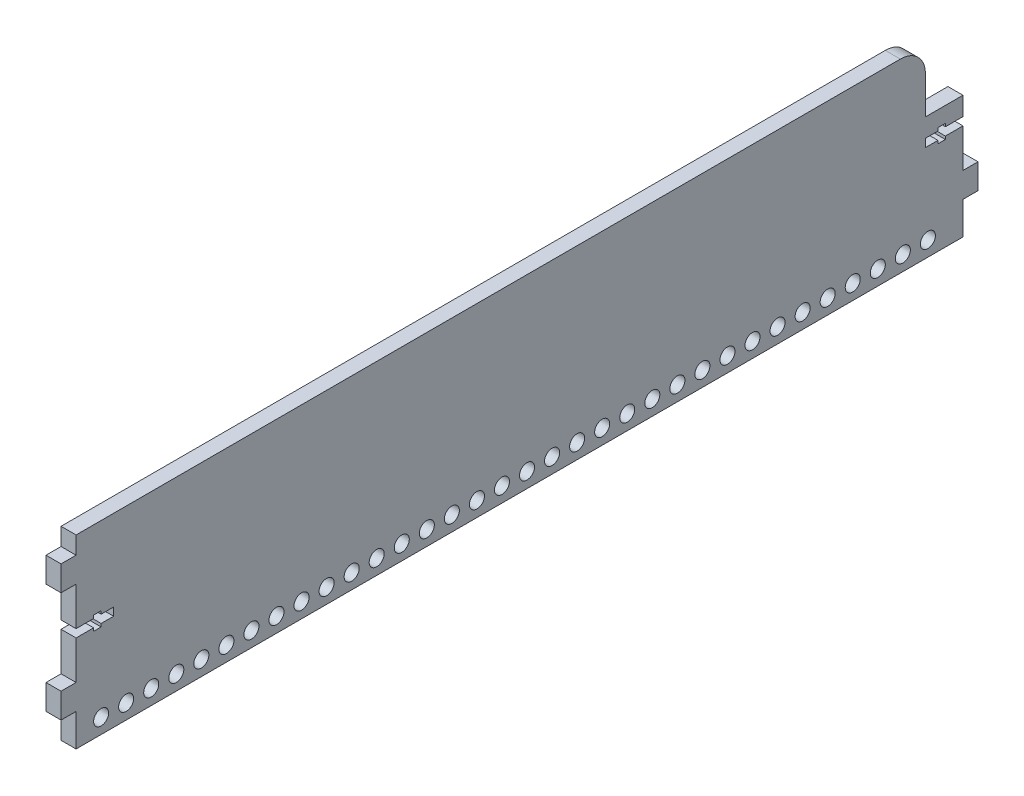
SolidWorks part; units mm, degrees
ref_plane "Front Plane" through (0, 0, 0) normal (0, 0, 1) x (1, 0, 0)
ref_plane "Top Plane" through (0, 0, 0) normal (0, 1, 0) x (1, 0, 0)
ref_plane "Right Plane" through (0, 0, 0) normal (1, 0, 0) x (0, 0, -1)
sketch "Sketch1" plane through (0, 0, 0) normal (1, 0, 0) x (0, 0, -1)
  line L1 (-177, -40) -> (177, -40)
  line L2 (-177, -40) -> (-177, 40)
  line L3 (-177, 40) -> (177, 40)
  line L4 (177, -40) -> (177, 40)
  line L5 (-177, -40) -> (177, 40) construction
  line L6 (-177, 40) -> (177, -40) construction
  point P0 (0, 0)
  dimension "D1" = 80
  dimension "D2" = 354
extrude "Boss-Extrude1" add sketch "Sketch1" along normal blind 6
sketch "Sketch4" plane through (0, 0, 177) normal (0, 0, 1) x (1, 0, 0)
  line L1 (6, 27) -> (0, 27) construction
  line L2 (6, 17) -> (6, 27) construction
  line L3 (0, 27) -> (0, 17) construction
  line L4 (0, 17) -> (6, 17) construction
  line L7 (6, -17) -> (0, -17) construction
  line L8 (6, -27) -> (6, -17) construction
  line L9 (0, -17) -> (0, -27) construction
  line L10 (0, -27) -> (6, -27) construction
  line L13 (6, 27) -> (0, 27)
  line L14 (6, 17) -> (6, 27)
  line L15 (0, 27) -> (0, 17)
  line L16 (0, 17) -> (6, 17)
  line L17 (6, -17) -> (0, -17)
  line L18 (6, -27) -> (6, -17)
  line L19 (0, -17) -> (0, -27)
  line L20 (0, -27) -> (6, -27)
extrude "Boss-Extrude2" add sketch "Sketch4" along normal blind 6
sketch "Sketch5" plane through (0, 0, 0) normal (-1, 0, 0) x (0, 0, 1)
  line L0 (177, 17) -> (177, -17) construction
  line L7 (0, 0) -> (0, -20.5925) construction
  line L8 (-177, 1.6) -> (-170, 1.6)
  line L9 (-167, 2.8) -> (-170, 2.8)
  line L10 (-167, 1.6) -> (-162, 1.6)
  line L11 (-162, -1.6) -> (-162, 1.6)
  line L12 (-167, -1.6) -> (-162, -1.6)
  line L13 (-167, -2.8) -> (-170, -2.8)
  line L14 (-177, -1.6) -> (-170, -1.6)
  line L15 (-170, -2.8) -> (-170, -1.6)
  line L16 (-170, 1.6) -> (-170, 2.8)
  line L17 (-167, 1.6) -> (-167, 2.8)
  line L18 (-167, -2.8) -> (-167, -1.6)
  line L19 (183, -1.6) -> (183, 1.6) construction
  line L20 (183, -1.6) -> (183, 1.6)
  line L21 (183, 0) -> (146.4296, 0) construction
  line L25 (177, -1.6) -> (177, 1.6)
  line L26 (167, -2.8) -> (167, -1.6)
  line L27 (167, 1.6) -> (167, 2.8)
  line L28 (170, 1.6) -> (170, 2.8)
  line L29 (170, -2.8) -> (170, -1.6)
  line L30 (177, -1.6) -> (170, -1.6)
  line L31 (167, -2.8) -> (170, -2.8)
  line L32 (167, -1.6) -> (162, -1.6)
  line L33 (162, -1.6) -> (162, 1.6)
  line L34 (167, 1.6) -> (162, 1.6)
  line L35 (167, 2.8) -> (170, 2.8)
  line L36 (177, 1.6) -> (170, 1.6)
  line L37 (-177, -1.6) -> (-177, 1.6)
  line L38 (-183, -1.6) -> (-183, 1.6)
  point P0 (177, 0)
  dimension "D1" = 15
  dimension "D2" = 5.6
  dimension "D3" = 3.2
  dimension "D4" = 7
  dimension "D5" = 3
extrude "Cut-Extrude3" cut sketch "Sketch5" against normal up to next contours L25 L36 L28 L35 L27 L34 L33 L32 L26 L31 L29 L30 | L37 L14 L15 L13 L18 L12 L11 L10 L17 L9 L16 L8 region at (0, 0, -169.3696) region at (0, 0, 169.3696)
sketch "Sketch7" plane through (0, 0, -177) normal (0, 0, -1) x (-1, 0, 0)
  line L6 (-6, -17) -> (0, -17)
  line L7 (-6, -17) -> (-6, -27)
  line L8 (-6, -27) -> (0, -27)
  line L9 (0, -17) -> (0, -27)
  line L15 (-6, -40) -> (-6, -1.6) construction
  line L16 (0, -40) -> (0, -1.6) construction
  line L17 (-6, -17) -> (0, -17) construction
  line L18 (0, -27) -> (-6, -27) construction
extrude "Boss-Extrude3" add sketch "Sketch7" along normal blind 6
sketch "Sketch8" plane through (0, 40, 0) normal (0, 1, 0) x (1, 0, 0)
  line L1 (0, 177) -> (6, 177)
  line L2 (0, 177) -> (0, -177)
  line L3 (0, -177) -> (6, -177)
  line L4 (6, 177) -> (6, -177)
extrude "Cut-Extrude4" cut sketch "Sketch8" against normal blind 6
sketch "Sketch9" plane through (0, 34, 0) normal (0, 1, 0) x (1, 0, 0)
  line L0 (0, 177) -> (0, -177) construction
  line L1 (0, 177) -> (6, 177)
  line L2 (0, 177) -> (0, 162)
  line L3 (0, 162) -> (6, 162)
  line L4 (6, 177) -> (6, 162)
  line L5 (6, -177) -> (6, 177) construction
  dimension "D2" = 15
extrude "Cut-Extrude5" cut sketch "Sketch9" against normal blind 25
fillet "Fillet1" radius 10 1 edges at (3, 34, -162)
sketch "Sketch10" plane through (0, 0, 0) normal (-1, 0, 0) x (0, 0, 1)
  line L0 (177, -40) -> (-177, -40) construction
  line L1 (177, -27) -> (177, -40) construction
  circle A0 centre (167, -34) radius 3
  circle A1 centre (157, -34) radius 3
  circle A2 centre (147, -34) radius 3
  circle A3 centre (137, -34) radius 3
  circle A4 centre (127, -34) radius 3
  circle A5 centre (117, -34) radius 3
  circle A6 centre (107, -34) radius 3
  circle A7 centre (97, -34) radius 3
  circle A8 centre (87, -34) radius 3
  circle A9 centre (77, -34) radius 3
  circle A10 centre (67, -34) radius 3
  circle A11 centre (57, -34) radius 3
  circle A12 centre (47, -34) radius 3
  circle A13 centre (37, -34) radius 3
  circle A14 centre (27, -34) radius 3
  circle A15 centre (17, -34) radius 3
  circle A16 centre (7, -34) radius 3
  circle A17 centre (-3, -34) radius 3
  circle A18 centre (-13, -34) radius 3
  circle A19 centre (-23, -34) radius 3
  circle A20 centre (-33, -34) radius 3
  circle A21 centre (-43, -34) radius 3
  circle A22 centre (-53, -34) radius 3
  circle A23 centre (-63, -34) radius 3
  circle A24 centre (-73, -34) radius 3
  circle A25 centre (-83, -34) radius 3
  circle A26 centre (-93, -34) radius 3
  circle A27 centre (-103, -34) radius 3
  circle A28 centre (-113, -34) radius 3
  circle A29 centre (-123, -34) radius 3
  circle A30 centre (-133, -34) radius 3
  circle A31 centre (-143, -34) radius 3
  circle A32 centre (-153, -34) radius 3
  circle A33 centre (-163, -34) radius 3
  dimension "D1" = 6
  dimension "D2" = 6
  dimension "D3" = 10
  dimension "D4" = 34
extrude "Cut-Extrude6" cut sketch "Sketch10" against normal up to next (6 mm away)
